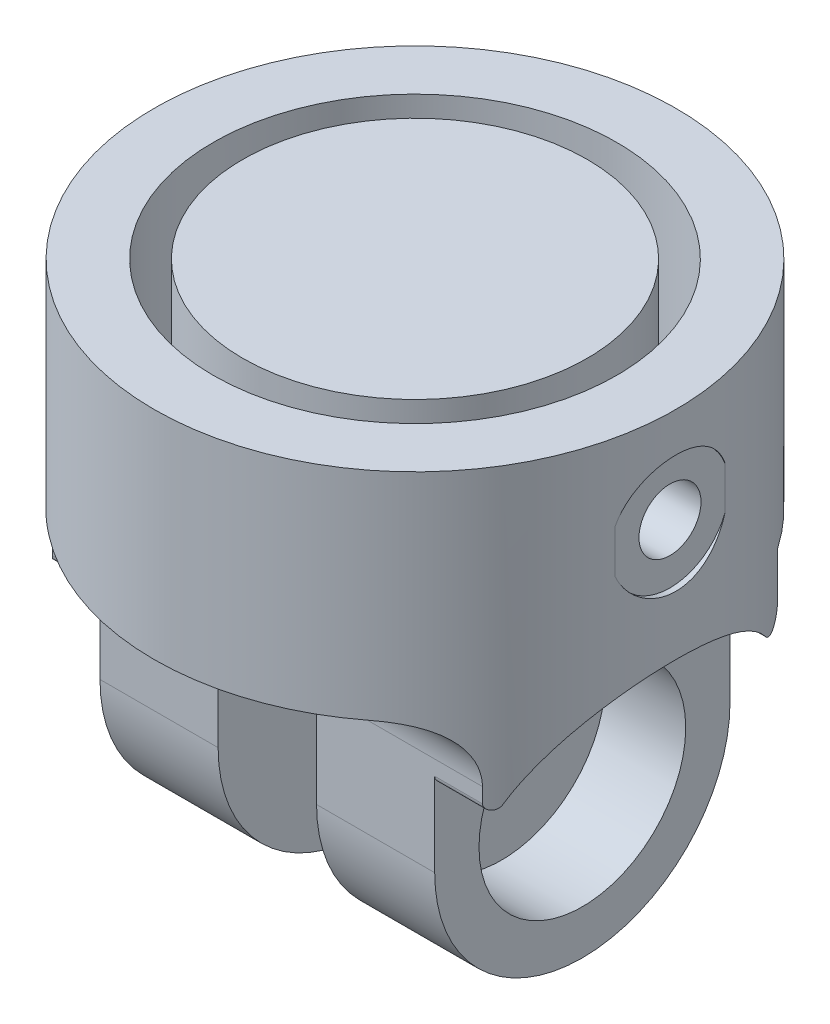
SolidWorks part; units mm, degrees
material "PLA Black"
ref_plane "Front" through (0, 0, 0) normal (0, 0, 1) x (1, 0, 0)
ref_plane "Top" through (0, 0, 0) normal (0, 1, 0) x (1, 0, 0)
ref_plane "Right" through (0, 0, 0) normal (1, 0, 0) x (0, 0, -1)
sketch "Sketch1" plane through (0, 0, 0) normal (0, 1, 0) x (1, 0, 0)
  line L0 (0, 8.75) -> (0, 10.25) construction
  circle A0 centre (0, 0) radius 10.25
  circle A1 centre (0, 0) radius 13.25
  circle A2 centre (0, 0) radius 9.5 construction
  circle A4 centre (0, 0) radius 8.75
  point P11 (0, 9.5)
  dimension "D1" = 1.5
  dimension "D2" = 3
  dimension "D3" = 19
extrude "Boss-Extrude1" add sketch "Sketch1" along normal blind 10 contours A1 A0 | A4 region at (-12.8752, 0, 0) region at (0, 0, 0)
sketch "Sketch3" plane through (0, 0, 0) normal (0, -1, 0) x (1, 0, 0)
  circle A2 centre (0, 0) radius 13.25 construction
  circle A3 centre (0, 0) radius 13.25
extrude "Boss-Extrude2" add sketch "Sketch3" along normal blind 1
sketch "Sketch4" plane through (0, -1, 0) normal (0, -1, 0) x (1, 0, 0)
  line L0 (0, 17.8908) -> (0, -17.0763) construction
  line L1 (2.5, 7.5) -> (8.5, 7.5)
  line L2 (2.5, 7.5) -> (2.5, -7.5)
  line L3 (2.5, -7.5) -> (8.5, -7.5)
  line L4 (8.5, 7.5) -> (8.5, -7.5)
  line L5 (-8.5, 7.5) -> (-8.5, -7.5)
  line L6 (-2.5, -7.5) -> (-8.5, -7.5)
  line L7 (-2.5, 7.5) -> (-2.5, -7.5)
  line L8 (-2.5, 7.5) -> (-8.5, 7.5)
  line L9 (16.8049, 0) -> (-19.8998, 0) construction
  dimension "D1" = 6
  dimension "D2" = 5
  dimension "D3" = 15
extrude "Boss-Extrude3" add sketch "Sketch4" along normal blind 16
sketch "Sketch5" plane through (8.5, 0, 0) normal (1, 0, 0) x (0, 0, -1)
  line L0 (-7.5, -17) -> (-7.5, -1) construction
  line L1 (7.5, -17) -> (7.5, -1) construction
  line L2 (7.5, -9) -> (7.5, -17.1619)
  line L3 (7.5, -17.1619) -> (-7.5, -17.1619)
  line L4 (-7.5, -17.1619) -> (-7.5, -9)
  arc A0 (-7.5, -9) -> (7.5, -9) centre (0, -9) ccw
  circle A1 centre (0, -9) radius 1.75
  dimension "D1" = 3.5
extrude "Cut-Extrude1" cut sketch "Sketch5" against normal through all both and the other way through all
sketch "Sketch6" plane through (8.5, 0, 0) normal (1, 0, 0) x (0, 0, -1)
  circle A0 centre (0, -9) radius 5.25
  dimension "D1" = 10.5
extrude "Cut-Extrude2" cut sketch "Sketch6" against normal blind 4.1
mirror "Mirror1" about plane through (0, 0, 0) normal (1, 0, 0) of "Cut-Extrude2"
ref_plane "Plane9" through (2.25, 0, 0) normal (1, 0, 0) x (0, 0, -1)
sketch "Sketch7" plane through (2.25, 0, 0) normal (1, 0, 0) x (0, 0, -1)
  line L0 (3.6, -9) -> (3.6, -1) construction
  line L1 (7.5, -1) -> (-7.5, -1) construction
  line L2 (3.5026, -8.1681) -> (1.8, -1) construction
  line L3 (3.2149, -7.38) -> (0, -1) construction
  line L4 (1.8, -0.6757) -> (1.8, -1.4422) construction
  line L5 (2.8087, -6.748) -> (-1.8, -1) construction
  line L6 (2.3875, -6.3056) -> (-3.6, -1) construction
  line L8 (0, -1.6788) -> (0, 0) construction
  line L9 (-8.4824, -9) -> (8.712, -9) construction
  line L10 (2.0173, -6.0183) -> (-5.4, -1) construction
  line L11 (-3.6, -0.3587) -> (-3.6, -1.6788) construction
  circle A0 centre (0, -9) radius 3.6 construction
  dimension "D1" = 7.2
  dimension "D2" = 34.081
  dimension "D3" = 8
ref_plane "Plane1" through (2.25, -1, -3.6) normal (0, 1, 0) x (1, 0, 0)
ref_plane "Plane2" through (2.25, -1, -1.8) normal (0, 0.9729, 0.2311) x (1, 0, 0)
ref_plane "Plane3" through (2.25, -1, 0) normal (0, 0.893, 0.45) x (1, 0, 0)
ref_plane "Plane5" through (2.25, -1, 1.8) normal (0, 0.7802, 0.6255) x (1, 0, 0)
ref_plane "Plane6" through (2.25, -1, 3.6) normal (0, 0.6632, 0.7484) x (1, 0, 0)
ref_plane "Plane7" through (2.25, -1, 5.4) normal (0, 0.5604, 0.8282) x (1, 0, 0)
sketch "Sketch8" plane through (2.25, -1, -3.6) normal (0, 1, 0) x (1, 0, 0)
  circle A0 centre (0, 0) radius 0.825
  dimension "D1" = 1.65
extrude "Cut-Extrude5" cut sketch "Sketch8" along normal blind 5.5 and the other way through all
sketch "Sketch9" plane through (2.25, -1, -1.8) normal (0, 0.9729, 0.2311) x (1, 0, 0)
  circle A0 centre (0, 0) radius 0.825
  dimension "D1" = 1.65
extrude "Cut-Extrude3" cut sketch "Sketch9" along normal blind 5.5
sketch "Sketch10" plane through (2.25, -1, 0) normal (0, 0.893, 0.45) x (1, 0, 0)
  circle A0 centre (0, 0) radius 0.825
  dimension "D1" = 1.65
sketch "Sketch11" plane through (2.25, -1, 1.8) normal (0, 0.7802, 0.6255) x (1, 0, 0)
  circle A0 centre (0, 0) radius 0.825
  dimension "D1" = 1.65
sketch "Sketch12" plane through (2.25, -1, 3.6) normal (0, 0.6632, 0.7484) x (1, 0, 0)
  circle A0 centre (0, 0) radius 0.825
  dimension "D1" = 1.65
sketch "Sketch14" plane through (2.25, -1, 5.4) normal (0, 0.5604, 0.8282) x (1, 0, 0)
  circle A0 centre (0, 0) radius 0.825
  dimension "D1" = 1.65
extrude "Cut-Extrude6" cut sketch "Sketch10" along normal blind 5.5 and the other way through all
extrude "Cut-Extrude7" cut sketch "Sketch11" along normal blind 5.5 and the other way through all contours A0
extrude "Cut-Extrude8" cut sketch "Sketch12" along normal blind 5.5 and the other way through all contours A0
extrude "Cut-Extrude9" cut sketch "Sketch14" along normal blind 5.5 and the other way through all contours A0
ref_plane "Plane8" through (13.25, 0, 0) normal (1, 0, 0) x (0, 0, -1)
hole_wizard "Tap Drill for M3 Helicoil1" positions "Sketch17" profile "Sketch18" hole size "M3x0.5" standard "DIN"
sketch "Sketch17" plane through (13.25, 0, 0) normal (1, 0, 0) x (0, 0, -1)
  line L0 (-22.2973, 5) -> (18.0703, 5) construction
  line L4 (0, 12.2732) -> (0, -5.3405) construction
  line L6 (-7.5, -9) -> (-7.5, -1) construction
  line L7 (7.5, -9) -> (7.5, -1) construction
  line L8 (13.25, 10) -> (-13.25, 10) construction
  line L9 (10.25, 0) -> (-10.25, 0) construction
  point P0 (0, 5)
sketch "Sketch18" plane through (13.25, 5, 0) normal (0, 1, 0) x (0, 0, -1)
  line L0 (0, 0) -> (0, 6.9464)
  line L1 (0, 6.9464) -> (1.575, 6)
  line L2 (1.575, 6) -> (1.575, 0)
  line L5 (1.575, 0) -> (0, 0)
  line L10 (0, 6.9464) -> (-1.575, 6) construction
  line L11 (0, -6.35) -> (0, 107.95) construction
  dimension "Hole Dia." = 3.15
  dimension "Hole Depth" = 6
  dimension "Drill Angle" = 118
sketch "Sketch20" plane through (13.25, 0, 0) normal (1, 0, 0) x (0, 0, -1)
  circle A0 centre (0, 5) radius 3
  dimension "D1" = 6
extrude "Cut-Extrude10" cut sketch "Sketch20" against normal blind 0.3
sketch "Sketch21" plane through (8.5, 0, 0) normal (1, 0, 0) x (0, 0, -1)
  line L0 (7.5, -1) -> (-7.5, -1) construction
  line L1 (7.5, -0.1252) -> (7.5, -3.188)
  line L2 (0.9244, -19.5662) -> (-4.8209, -14.7453) construction
  line L3 (0, 5.2718) -> (0, -9.2894) construction
  line L4 (0, 10) -> (0, -1) construction
  line L5 (-7.5, -0.1252) -> (-7.5, -4.7575)
  line L6 (7.5, -0.1252) -> (-7.5, -0.1252)
  line L7 (-7.5, -9) -> (-7.5, -1) construction
  line L8 (7.5, -9) -> (7.5, -1) construction
  line L9 (0, -1) -> (9.1102, -5.2607) construction
  line L10 (0, -1) -> (1.2641, -0.2702) construction
  line L11 (6.0277, -3.7401) -> (7.5, -3.188) construction
  line L12 (10.5662, -8.0756) -> (4.8209, -3.2547) construction
  line L13 (-4.8209, -14.7453) -> (4.8209, -3.2547) construction
  line L14 (10.5662, -8.0756) -> (0.9244, -19.5662) construction
  arc A0 (-6.8849, -4.9259) -> (6.0277, -3.7401) centre (0, -9) cw
  arc A1 (-6.8849, -4.9259) -> (-7.5, -4.7575) centre (-7.1694, -4.7575) cw
  arc A2 (7.5, -3.188) -> (6.0277, -3.7401) centre (6.6603, -3.188) cw
  circle A3 centre (0, -9) radius 1.75 construction
  arc A4 (-4.8209, -14.7453) -> (4.8209, -3.2547) centre (0, -9) cw construction
  dimension "D1" = 30
  dimension "D3" = 7.5
  dimension "D2" = 50
  dimension "D4" = 15
extrude "Boss-Extrude4" add sketch "Sketch21" along normal up to surface (2.423 mm away) up to face at (13.0965, 5, 0)
mirror "Mirror2" about plane through (0, 0, 0) normal (1, 0, 0) of "Boss-Extrude4", "Tap Drill for M3 Helicoil1", "Cut-Extrude10"
fillet "Fillet1" radius 3 2 edges at (-6.7115, -1, 7.5) (6.7115, -1, 7.5)
equation "\"knee_angle\"= 0"
equation "\"ankle_angle\" = 90"
equation "\"hip_angle\" = 0"
equation "\"spring_ankle_parallel_arm_diameter\"= 1.5"
equation "\"spring_ankle_parallel_arm_length\"= 13"
equation "\"spring_ankle_parallel_intern_diameter\"= 5.7"
equation "\"spring_ankle_parallel_angle\"= \"ankle_angle\""
equation "\"spring_ankle_parallel_turns\"= 3"
equation "\"spring_ankle_parallel_pitch\"= \"spring_ankle_parallel_arm_diameter\" * 1.01"
equation "\"spring_ankle_parallel_cutting_distance\"= (1-\"spring_ankle_parallel_angle\" / 360) * \"spring_ankle_parallel_pitch\""
equation "\"spring_ankle_serial_arm_diameter\"= 1.91"
equation "\"spring_ankle_serial_arm_length\"= 10"
equation "\"spring_ankle_serial_intern_diameter\"= 5.7"
equation "\"spring_ankle_serial_angle\"= \"90\""
equation "\"spring_ankle_serial_turns\"= 3"
equation "\"spring_ankle_serial_pitch\"= \"spring_ankle_serial_arm_diameter\" * 1.01"
equation "\"spring_ankle_serial_cutting_distance\"= (1-\"spring_ankle_serial_angle\" / 360) * \"spring_ankle_serial_pitch\""
equation "\"spring_knee_parallel_arm_diameter\"= 1.5"
equation "\"spring_knee_parallel_arm_length\"= 13"
equation "\"spring_knee_parallel_intern_diameter\"= 5.7"
equation "\"spring_knee_parallel_angle\"= -\"knee_angle\" + 90"
equation "\"spring_knee_parallel_turns\"= 3"
equation "\"spring_knee_parallel_pitch\"= \"spring_knee_parallel_arm_diameter\" * 1.01"
equation "\"spring_knee_parallel_cutting_distance\"= (1-(\"spring_knee_parallel_angle\") / 360) * \"spring_knee_parallel_pitch\""
equation "\"spring_knee_serial_arm_diameter\"= 1.91"
equation "\"spring_knee_serial_arm_length\"= 10"
equation "\"spring_knee_serial_intern_diameter\"= 5.7"
equation "\"spring_knee_serial_angle\"= \"90\""
equation "\"spring_knee_serial_turns\"= 3"
equation "\"spring_knee_serial_pitch\"= \"spring_knee_serial_arm_diameter\" * 1.01"
equation "\"spring_knee_serial_cutting_distance\"= (1-\"spring_knee_serial_angle\" / 360) * \"spring_knee_serial_pitch\""
equation "\"spring_ankle_parallel_nominal_diameter\"= \"spring_ankle_parallel_arm_diameter\" + \"spring_ankle_parallel_intern_diameter\""
equation "\"spring_ankle_serial_nominal_diameter\"= \"spring_ankle_serial_arm_diameter\" + \"spring_ankle_serial_intern_diameter\""
equation "\"spring_knee_parallel_nominal_diameter\"= \"spring_knee_parallel_arm_diameter\" + \"spring_knee_parallel_intern_diameter\""
equation "\"spring_knee_serial_nominal_diameter\"= \"spring_knee_serial_arm_diameter\" + \"spring_knee_serial_intern_diameter\""
equation "\"D1@Sketch7\"=\"spring_ankle_parallel_nominal_diameter\""
equation "\"D1@Sketch8\"=\"spring_ankle_parallel_arm_diameter\"*1.1"
equation "\"D1@Sketch9\"=\"spring_ankle_parallel_arm_diameter\"*1.1"
equation "\"D1@Sketch10\"=\"spring_ankle_parallel_arm_diameter\"*1.1"
equation "\"D1@Sketch11\"=\"spring_ankle_parallel_arm_diameter\"*1.1"
equation "\"D1@Sketch12\"=\"spring_ankle_parallel_arm_diameter\"*1.1"
equation "\"D1@Sketch14\"=\"spring_ankle_parallel_arm_diameter\"*1.1"
equation "\"D1@Cut-Extrude3\"=\"spring_ankle_parallel_arm_length\"-\"axis_structure_distance\""
equation "\"axis_structure_distance\"= 7.5"
equation "\"D1@Cut-Extrude5\"=\"spring_ankle_parallel_arm_length\"-\"axis_structure_distance\""
equation "\"D1@Cut-Extrude6\"=\"spring_ankle_parallel_arm_length\"-\"axis_structure_distance\""
equation "\"D1@Cut-Extrude7\"=\"spring_ankle_parallel_arm_length\"-\"axis_structure_distance\""
equation "\"D1@Cut-Extrude8\"=\"spring_ankle_parallel_arm_length\"-\"axis_structure_distance\""
equation "\"D1@Cut-Extrude9\"=\"spring_ankle_parallel_arm_length\"-\"axis_structure_distance\""
equation "\"D1@Boss-Extrude3\"=\"axis_structure_distance\"*2"
equation "\"ankle_angle_max\" = 120"
equation "\"ankle_angle_min\" = 50"
equation "\"knee_angle_max\" = 120"
equation "\"knee_angle_min\" = 0"
equation "\"hip_angle_max\" = 90"
equation "\"hip_angle_min\" = -60"
equation "\"D1@Sketch21\"=\"ankle_angle_max\"-90"
equation "\"D2@Sketch21\"=\"ankle_angle_min\""
equation "\"D1@Plane9\"=(\"spring_ankle_parallel_arm_diameter\"*\"spring_ankle_parallel_turns\")/2"
